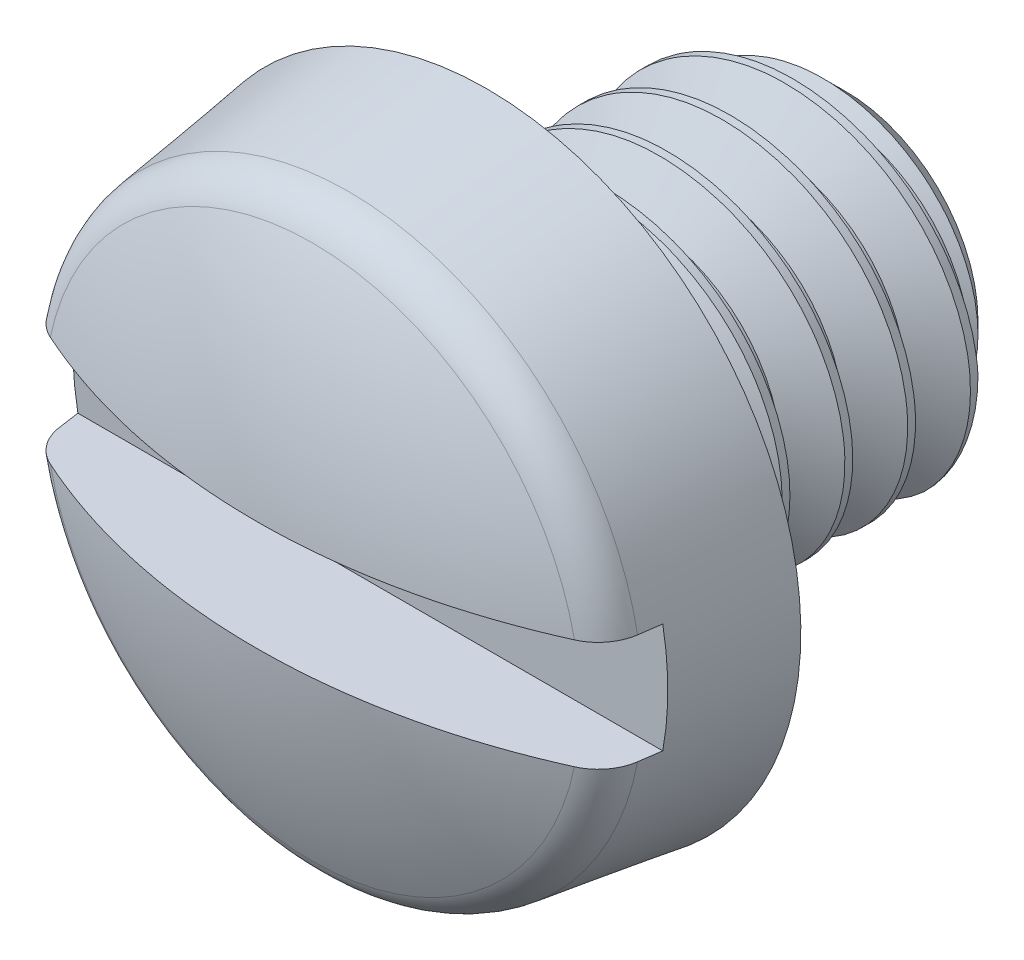
SolidWorks part; units mm, degrees
ref_plane "Front" through (0, 0, 0) normal (0, 0, 1) x (1, 0, 0)
ref_plane "Top" through (0, 0, 0) normal (0, 1, 0) x (1, 0, 0)
ref_plane "Right" through (0, 0, 0) normal (1, 0, 0) x (0, 0, -1)
sketch "Sketch1" plane through (0, 0, 0) normal (0, 0, 1) x (1, 0, 0)
  circle A0 centre (0, 0) radius 3.5
  dimension "Head Dia" = 7
extrude "Extrude3" add sketch "Sketch1" along normal blind 2.6
sketch "Sketch11" plane through (0, 0, 0) normal (1, 0, 0) x (0, 0, -1)
  line L0 (0, 0) -> (-2.854, 0) construction
  line L4 (-2.6, 3.5) -> (-2.6, -3.5) construction
  line L5 (-2.854, 3.64) -> (0, 3.64)
  line L7 (0, 3.64) -> (0, 3.5)
  line L8 (-1.5457, 3.2828) -> (0, 3.5)
  line L9 (0, -3.5) -> (0, 3.5) construction
  line L13 (-2.6, 0) -> (-2.854, 0)
  line L14 (-2.854, 0) -> (-2.854, 3.64)
  arc A0 (-1.9456, 2.9854) -> (-2.6, 0) centre (4.5368, 0) ccw
  arc A1 (-1.5457, 3.2828) -> (-1.9456, 2.9854) centre (-1.4733, 2.7678) ccw
  point P13 (-1.82, 3.2442)
  dimension "D1" = 0.52
  dimension "D3" = 0.254
  dimension "D5" = 0.14
  dimension "D2" = 0.78
  dimension "D4" = 8
revolve "Cut-Revolve3" cut sketch "Sketch11" angle 360 about L0
sketch "Sketch4" plane through (0, 0, 0) normal (1, 0, 0) x (0, 0, -1)
  line L0 (0, 0) -> (4, 0)
  line L3 (4, 0) -> (4, 2)
  line L4 (4, 2) -> (0, 2)
  line L6 (0, 2) -> (0, 0)
  line L9 (4, 2) -> (4, -2) construction
  dimension "length" = 4
  dimension "dia" = 4
revolve "Revolve1" add sketch "Sketch4" angle 360 about L0
sketch "Sketch13" plane through (0, 0, -4) normal (0, 0, -1) x (-1, 0, 0)
  circle A2 centre (0, 0) radius 2
curve "Helix/Spiral1" pitch 0.7 height 4 radius 2 centre (0, 0, -4) axis (0, 0, 1) start towards (0, 1, 0)
chamfer "Chamfer1" distance 0.525 angle 45 1 edges at (2, 0, -4)
sketch "Sketch14" plane through (0, 0, 0) normal (1, 0, 0) x (0, 0, -1)
  line L0 (4, 2) -> (4.6125, 2)
  line L1 (4.6125, 2) -> (4.35, 1.5453)
  line L2 (4.35, 1.5453) -> (4.2625, 1.5453)
  line L3 (4.2625, 1.5453) -> (4, 2)
  line L4 (4.1312, 1.7727) -> (4.4812, 1.7727) construction
  dimension "D1" = 0.0875
  dimension "D2" = 60
  dimension "D3" = 0.35
sweep "Cut-Sweep1" cut profiles "Sketch14" path "Helix/Spiral1" align with end faces yes
ref_plane "Plane1" through (0, 0, 34.1) normal (0, 0, -1) x (-1, 0, 0)
sketch "Sketch29" [suppressed] plane through (0, 0, 28.575) normal (0, 0, -1) x (-1, 0, 0)
  circle A0 centre (0, 0) radius 1.7526 construction
  circle A1 centre (0, 0) radius 1.7526
  point P3 (0, -1.7526)
  point P4 (0, 1.7526)
extrude "Extrude11" [suppressed] add sketch "Sketch29" against normal up to surface (28.575 mm away) up to plane "Front"
ref_plane "Plane2" through (0, 0, 2.6) normal (0, 0, 1) x (1, 0, 0)
sketch "Sketch32" plane through (0, 0, 2.6) normal (0, 0, 1) x (1, 0, 0)
  line L0 (-3.5, 0.6125) -> (3.5, -0.6125) construction
  line L1 (-3.5, 0.6125) -> (3.5, 0.6125)
  line L2 (-3.5, 0.6125) -> (-3.5, -0.6125)
  line L3 (-3.5, -0.6125) -> (3.5, -0.6125)
  line L4 (3.5, 0.6125) -> (3.5, -0.6125)
  circle A0 centre (0, 0) radius 3.5 construction
  dimension "D1" = 1.225
extrude "Extrude16" cut sketch "Sketch32" against normal blind 1.3
sketch "Sketch18" plane through (0, 0, 0) normal (1, 0, 0) x (0, 0, -1)
  line L1 (4, 2) -> (0, 2) construction
  point P0 (2.95, -2)
  point P1 (3.3, 2)
  point P2 (-2.6, 0.6125)
  dimension "D1" = 0.7
  dimension "D2" = 1.05
other "DeleteFace1" [suppressed]
equation "\"D3@Helix/Spiral1\" = \"length@Sketch4\""
equation "\"D1@Sketch14\" = \"D4@Helix/Spiral1\" * .125"
equation "\"D3@Sketch14\" = \"D4@Helix/Spiral1\" * .5"
equation "\"D5@Sketch11\" = \"Head Dia@Sketch1\" * .02"
equation "\"D1@Sketch18\" = \"D4@Helix/Spiral1\""
equation "\"D2@Sketch18\" = \"D4@Helix/Spiral1\" * 1.5"
equation "\"D2@Sketch11\" = \"Head Ht@Extrude3\" * .3"
equation "\"D1@Extrude16\" = \"Head Ht@Extrude3\" * .5"
equation "\"D1@Sketch11\" = \"Head Ht@Extrude3\" * .2"
equation "\"D1@Sketch32\" = \"D4@Helix/Spiral1\" * 1.75"
equation "\"D1@Chamfer1\"= \"D4@Helix/Spiral1\" * .75"
